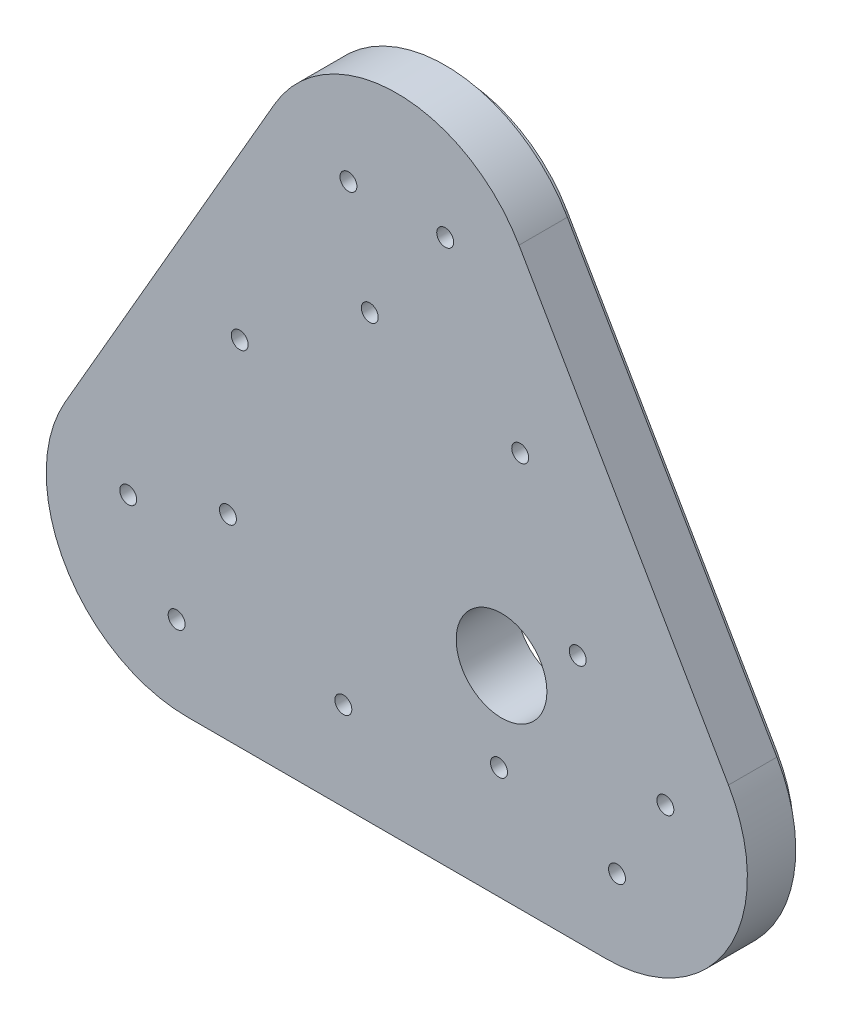
SolidWorks part; units mm, degrees
ref_plane "Plano frontal" through (0, 0, 0) normal (0, 0, 1) x (1, 0, 0)
ref_plane "Plano superior" through (0, 0, 0) normal (0, 1, 0) x (1, 0, 0)
ref_plane "Plano direito" through (0, 0, 0) normal (1, 0, 0) x (0, 0, -1)
sketch "Esboço1" plane through (0, 0, 0) normal (0, 0, 1) x (1, 0, 0)
  line L0 (0, 0) -> (0, 60) construction
  line L1 (0, 0) -> (-51.9615, -30) construction
  line L2 (0, 0) -> (51.9615, -30) construction
  line L3 (0, 0) -> (0, -52.5079) construction
  line L4 (0, 0) -> (45.4731, 26.2539) construction
  line L5 (0, 0) -> (-45.4731, 26.2539) construction
  line L6 (-12, 70) -> (12, 70) construction
  line L7 (-66.6218, -24.6077) -> (-54.6218, -45.3923) construction
  line L8 (-51.9615, -30) -> (-60.6218, -35) construction
  line L9 (0, 60) -> (0, 70) construction
  line L10 (51.9615, -30) -> (60.6218, -35) construction
  line L11 (54.6218, -45.3923) -> (66.6218, -24.6077) construction
  line L12 (31.8335, -36.8427) -> (39.8285, -22.995) construction
  line L13 (47.8235, -9.1473) -> (39.8285, -22.995) construction
  line L14 (-30.3109, 77.5) -> (-82.2724, -12.5)
  line L15 (30.3109, 77.5) -> (82.2724, -12.5)
  line L16 (-51.9615, -65) -> (51.9615, -65)
  arc A1 (51.9615, -65) -> (82.2724, -12.5) centre (51.9615, -30) ccw
  arc A2 (30.3109, 77.5) -> (-30.3109, 77.5) centre (0, 60) ccw
  arc A3 (-82.2724, -12.5) -> (-51.9615, -65) centre (-51.9615, -30) ccw
  circle A10 centre (-12, 70) radius 2.1
  circle A11 centre (-66.6218, -24.6077) radius 2.1
  circle A12 centre (12, 70) radius 2.1
  circle A13 centre (-54.6218, -45.3923) radius 2.1
  circle A24 centre (66.6218, -24.6077) radius 2.1
  circle A25 centre (54.6218, -45.3923) radius 2.1
  circle A27 centre (25.9808, -15) radius 11.25
  point P25 (0, 70)
  point P40 (51.9615, -30)
  point P41 (51.9615, -30)
  point P45 (60.6218, -35)
  point P53 (25.9808, -15)
  dimension "D3" = 22.5
  dimension "D5" = 70
  dimension "D9" = 4.2
  dimension "D10" = 12
  dimension "D11" = 12
  dimension "D12" = 10
  dimension "D13" = 70
  dimension "D14" = 30
  dimension "D16" = 15.99
  dimension "D17" = 10
  dimension "D18" = 24
  dimension "D1" = 120
  dimension "D2" = 120
  dimension "D4" = 60
  dimension "D6" = 120
  dimension "D7" = 120
extrude "Ressalto-extrusão1" add sketch "Esboço1" along normal blind 15
sketch "Esboço2" plane through (0, 0, 0) normal (0, 0, -1) x (-1, 0, 0)
  line L0 (0, -65) -> (0, 0) construction
  line L1 (0, 0) -> (56.2917, 32.5) construction
  line L2 (0, 0) -> (-56.2917, 32.5) construction
  line L4 (51.9615, -65) -> (-51.9615, -65) construction
  line L5 (30.3109, 77.5) -> (82.2724, -12.5) construction
  line L6 (-82.2724, -12.5) -> (-30.3109, 77.5) construction
  circle A4 centre (38.9711, 22.5) radius 2.1
  circle A5 centre (41.8893, -16.4403) radius 2.1
  circle A6 centre (13.264, -43.0008) radius 2.1
  circle A7 centre (-25.3494, -37.1807) radius 2.1
  circle A8 centre (-44.8742, -3.3629) radius 2.1
  circle A9 centre (-30.6078, 32.9873) radius 2.1
  circle A10 centre (6.7069, 44.4974) radius 2.1
  point P31 (0, 0)
  dimension "D1" = 4.2
  dimension "D2" = 45
  dimension "D4" = 120
  dimension "D5" = 120
  dimension "D3" = 7
extrude "Corte-extrusão1" cut sketch "Esboço2" against normal up to surface (15 mm away) up to face at (37.2308, -15, 15)
sketch "Esboço4" plane through (0, 0, 0) normal (0, 0, -1) x (-1, 0, 0)
  line L0 (51.9615, -65) -> (-51.9615, -65) construction
  line L1 (30.3109, 77.5) -> (82.2724, -12.5) construction
  line L2 (-82.2724, -12.5) -> (-30.3109, 77.5) construction
  line L3 (51.9615, -65) -> (-51.9615, -65)
  line L4 (30.3109, 77.5) -> (82.2724, -12.5)
  line L5 (-82.2724, -12.5) -> (-30.3109, 77.5)
  line L9 (51.9615, -61.5) -> (-51.9615, -61.5)
  line L10 (-79.2413, -14.25) -> (-27.2798, 75.75)
  line L11 (27.2798, 75.75) -> (79.2413, -14.25)
  arc A0 (-82.2724, -12.5) -> (-51.9615, -65) centre (-51.9615, -30) ccw construction
  arc A1 (51.9615, -65) -> (82.2724, -12.5) centre (51.9615, -30) ccw construction
  arc A2 (30.3109, 77.5) -> (-30.3109, 77.5) centre (0, 60) ccw construction
  arc A3 (-82.2724, -12.5) -> (-51.9615, -65) centre (-51.9615, -30) ccw
  arc A4 (51.9615, -65) -> (82.2724, -12.5) centre (51.9615, -30) ccw
  arc A5 (30.3109, 77.5) -> (-30.3109, 77.5) centre (0, 60) ccw
  arc A9 (-79.2413, -14.25) -> (-51.9615, -61.5) centre (-51.9615, -30) ccw
  arc A10 (27.2798, 75.75) -> (-27.2798, 75.75) centre (0, 60) ccw
  arc A11 (51.9615, -61.5) -> (79.2413, -14.25) centre (51.9615, -30) ccw
  dimension "D1" = 3.5
extrude "Corte-extrusão2" cut sketch "Esboço4" against normal blind 3
